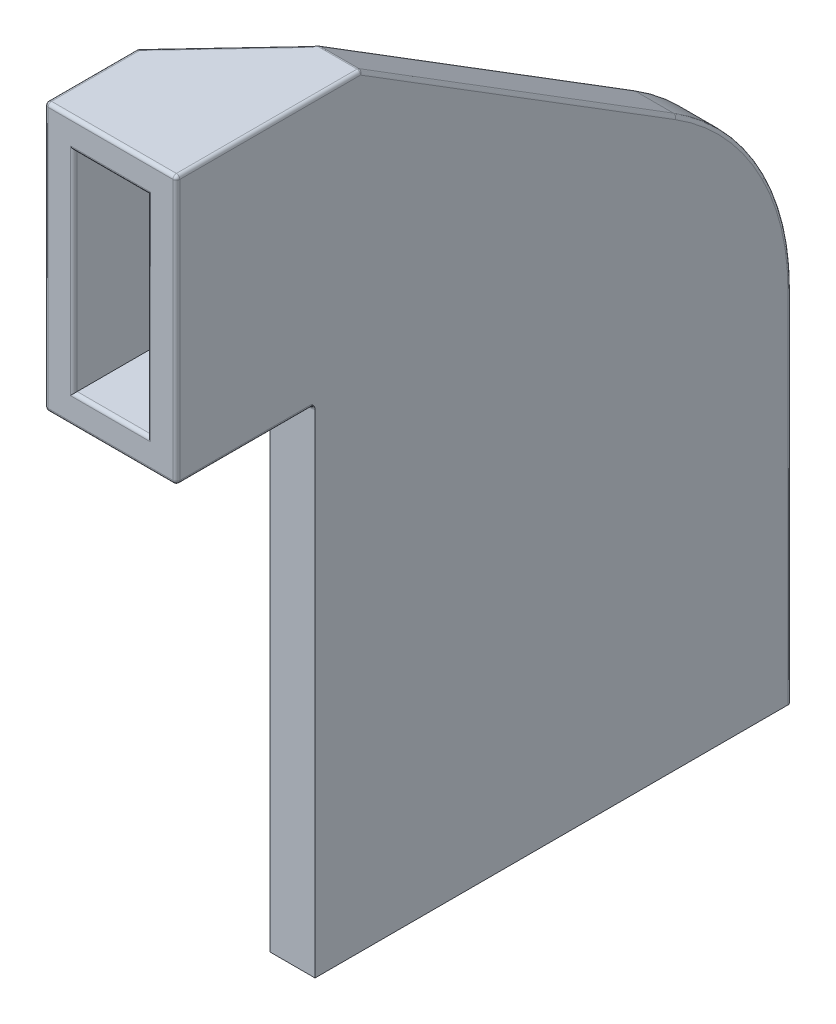
SolidWorks part; units mm, degrees
ref_plane "前视基准面" through (0, 0, 0) normal (0, 0, 1) x (1, 0, 0)
ref_plane "上视基准面" through (0, 0, 0) normal (0, 1, 0) x (1, 0, 0)
ref_plane "右视基准面" through (0, 0, 0) normal (1, 0, 0) x (0, 0, -1)
other "Configuration Table"
sketch "草图1" plane through (0, 0, 0) normal (1, 0, 0) x (0, 0, -1)
  line L0 (0, 0) -> (0, -3.86)
  line L1 (0, -3.86) -> (2, -3.86)
  line L2 (2, -3.86) -> (2, -11)
  line L3 (2, -11) -> (8.87, -11)
  line L4 (8.87, -11) -> (8.87, -5.8039)
  line L5 (7.2198, -2.8326) -> (2.67, 0)
  line L6 (2.67, 0) -> (0, 0)
  arc A0 (8.87, -5.8039) -> (7.2198, -2.8326) centre (5.37, -5.8039) ccw
  point P13 (8.87, -3.86)
  dimension "D5" = 3.5
  dimension "D1" = 3.86
  dimension "D2" = 2.67
  dimension "D3" = 6.87
  dimension "D4" = 2
  dimension "D6" = 11
extrude "凸台-拉伸1" add sketch "草图1" along normal blind 0.65
sketch "草图2" plane through (0, 0, 0) normal (0, 1, 0) x (1, 0, 0)
  line L0 (0, 2.67) -> (0, 0)
  line L1 (0, 2.67) -> (0, 0) construction
  line L2 (0.65, 2.67) -> (0, 2.67) construction
  line L3 (0, 0) -> (-1.25, 0)
  line L4 (-1.25, 0) -> (-1.25, 1.34)
  line L5 (-1.25, 1.34) -> (0, 2.67)
  line L6 (0.65, 2.67) -> (0.65, 0) construction
  dimension "D1" = 1.9
  dimension "D2" = 1.34
extrude "凸台-拉伸2" add sketch "草图2" against normal up to surface (3.86 mm away) up to face at (0.325, -3.86, -1)
shell "抽壳1" thickness 0.42 removed face at (-0.3, -1.93, 0)
fillet "圆角3" radius 0.05 15 edges at (-0.83, -1.93, 0) (-0.3, -3.44, 0) (0.23, -1.93, 0) (-0.3, -0.42, 0) (0.65, -1.93, 0) (-0.3, -3.86, 0) (-1.25, -1.93, 0) (-0.3, 0, 0) (-1.25, -1.93, -1.34) (0.65, 0, -1.335) (-0.625, 0, -2.005) (-1.25, 0, -0.67) (-0.625, -3.86, -2.005) (-1.25, -3.86, -0.67) (0.65, -3.86, -1)
fillet "圆角4" radius 0.05 10 edges at (0.6354, -3.8454, -2) (0.65, -8.4019, -8.87) (0.65, -4.1045, -8.4298) (0.3, 0, -2.67) (0.6354, -0.0146, -2.6935) (0, -8.4019, -8.87) (0, -4.1045, -8.4298) (0.3, -3.86, -2) (0.65, -1.4413, -4.9851) (0, -1.4163, -4.9449)
